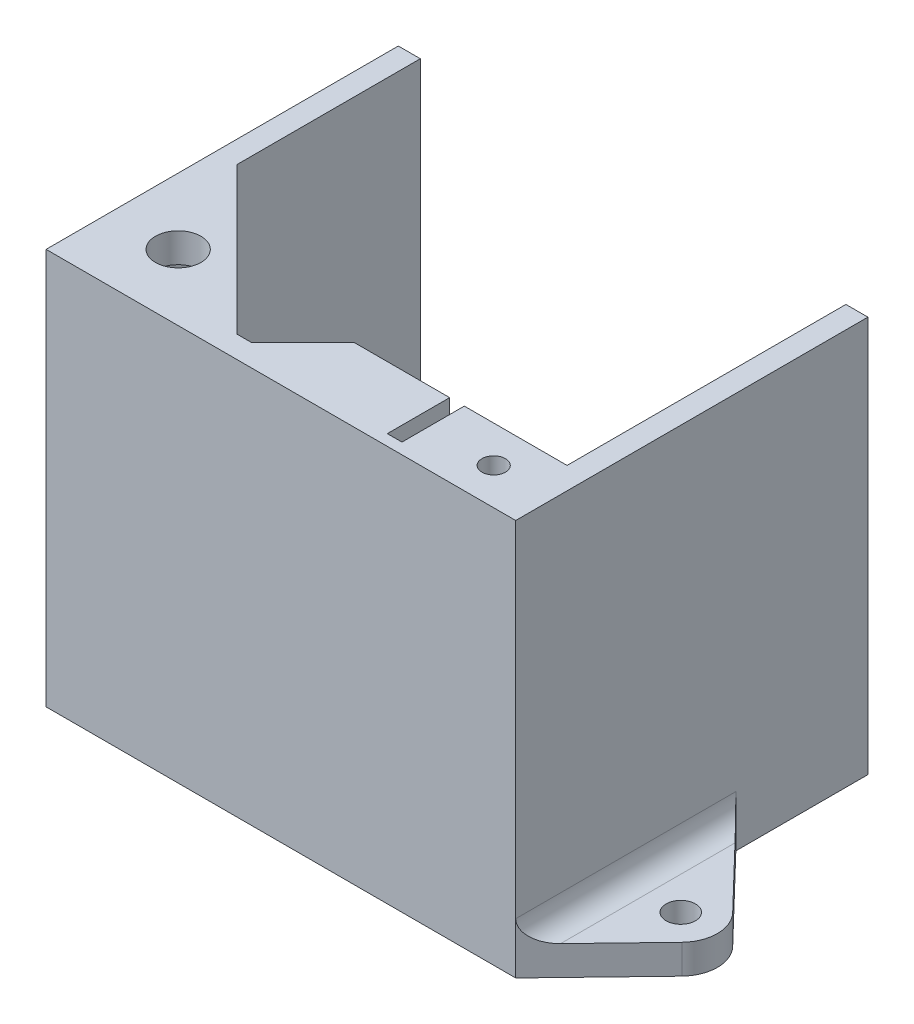
SolidWorks part; units mm, degrees
ref_plane "Płaszczyzna przednia" through (0, 0, 0) normal (0, 0, 1) x (1, 0, 0)
ref_plane "Płaszczyzna górna" through (0, 0, 0) normal (0, 1, 0) x (1, 0, 0)
ref_plane "Płaszczyzna prawa" through (0, 0, 0) normal (1, 0, 0) x (0, 0, -1)
sketch "Sketch1" plane through (0, 0, 0) normal (0, 1, 0) x (1, 0, 0)
  line L1 (-32, 24) -> (32, 24)
  line L2 (-32, 24) -> (-32, -24)
  line L3 (-32, -24) -> (32, -24)
  line L4 (32, 24) -> (32, -24)
  line L5 (-32, 24) -> (32, -24) construction
  line L6 (-32, -24) -> (32, 24) construction
  point P0 (0, 0)
  dimension "D1" = 64
  dimension "D2" = 48
extrude "Boss-Extrude1" add sketch "Sketch1" along normal blind 4
sketch "Sketch2" plane through (0, 0, 0) normal (0, -1, 0) x (1, 0, 0)
  line L9 (-20.6514, -16) -> (-22.3257, -13.1)
  line L10 (-22.3257, -13.1) -> (-25.6743, -13.1)
  line L11 (-25.6743, -13.1) -> (-27.3486, -16)
  line L12 (-27.3486, -16) -> (-25.6743, -18.9)
  line L13 (-25.6743, -18.9) -> (-22.3257, -18.9)
  line L14 (-22.3257, -18.9) -> (-20.6514, -16)
  line L15 (-32, -24) -> (-32, 24) construction
  line L16 (32, -24) -> (-32, -24) construction
  circle A0 centre (-24, -16) radius 2.9 construction
  dimension "D3" = 5.8
  dimension "D1" = 8
  dimension "D2" = 8
extrude "Cut-Extrude1" cut sketch "Sketch2" against normal blind 2.4
sketch "Sketch4" plane through (0, 0, 0) normal (0, -1, 0) x (1, 0, 0)
  line L0 (-32, -24) -> (-32, 24) construction
  line L1 (9.3486, 10) -> (7.6743, 12.9)
  line L2 (7.6743, 12.9) -> (4.3257, 12.9)
  line L3 (4.3257, 12.9) -> (2.6514, 10)
  line L4 (2.6514, 10) -> (4.3257, 7.1)
  line L5 (4.3257, 7.1) -> (7.6743, 7.1)
  line L6 (7.6743, 7.1) -> (9.3486, 10)
  line L8 (32, -24) -> (-32, -24) construction
  circle A0 centre (6, 10) radius 2.9 construction
  dimension "D3" = 5.8
  dimension "D1" = 38
  dimension "D2" = 34
extrude "Cut-Extrude2" cut sketch "Sketch4" against normal blind 2.4
sketch "Sketch6" plane through (0, 4, 0) normal (0, 1, 0) x (1, 0, 0)
  line L0 (-29, 21) -> (-29, 24)
  line L1 (-32, 24) -> (32, 24)
  line L2 (-32, 24) -> (-32, -24)
  line L3 (-32, -24) -> (32, -24)
  line L4 (32, 24) -> (32, -24)
  line L5 (-29, 21) -> (29, 21)
  line L6 (-29, 21) -> (-29, -21)
  line L7 (-29, -21) -> (29, -21)
  line L8 (29, 21) -> (29, -21)
  line L9 (-29, 21) -> (29, -21) construction
  line L10 (-29, -21) -> (29, 21) construction
  line L11 (29, 21) -> (29, 24)
  point P6 (0, 0)
  line M1 (32, -24) -> (32, 24)
  line M2 (32, 24) -> (-32, 24)
  line M3 (-32, 24) -> (-32, -24)
  line M4 (-32, -24) -> (32, -24)
  dimension "D1" = 58
  dimension "D2" = 42
extrude "Boss-Extrude3" add sketch "Sketch6" along normal blind 50 contours L11 L8 L7 L6 L0 M2 M3 M4 M1 region at (-29.8, 4, 0)
sketch "Sketch9" plane through (0, 4, 0) normal (0, 1, 0) x (1, 0, 0)
  line L0 (1, -13) -> (-7, -21)
  line L3 (29, -13) -> (1, -13)
  line L5 (-29, -21) -> (29, -21) construction
  line L6 (-7, -21) -> (29, -21)
  line L7 (1, -13) -> (-7, -21)
  line L9 (29, -21) -> (29, -13)
  line M3 (29, -21) -> (29, 24)
  line M6 (-29, -21) -> (29, -21)
  dimension "D1" = 8
  dimension "D2" = 8
  dimension "D3" = 28
extrude "Boss-Extrude4" add sketch "Sketch9" along normal blind 50 contours L3 L0 M3 M6 region at (12.9167, 4, 17.1667)
sketch "Sketch10" plane through (0, 0, 13) normal (0, 0, -1) x (-1, 0, 0)
  line L0 (-29, 54) -> (-29, 4) construction
  line L1 (-27, 39) -> (-1, 39)
  line L2 (-27, 39) -> (-27, 13)
  line L3 (-27, 13) -> (-1, 13)
  line L4 (-1, 39) -> (-1, 13)
  line L5 (-27, 39) -> (-1, 13) construction
  line L6 (-27, 13) -> (-1, 39) construction
  line L7 (-14, 39) -> (-14, 54) construction
  line L9 (-29, 54) -> (-1, 54) construction
  line L15 (-14.9986, 39) -> (-13.0014, 39)
  line L16 (-14.9986, 39) -> (-14.9986, 54)
  line L17 (-14.9986, 54) -> (-13.0014, 54)
  line L18 (-13.0014, 39) -> (-13.0014, 54)
  line L19 (-14.9986, 39) -> (-13.0014, 54) construction
  line L20 (-14.9986, 54) -> (-13.0014, 39) construction
  point P0 (-14, 26)
  point P9 (-14, 46.5)
  line M4 (-1, 4) -> (-1, 54)
  line M5 (-1, 54) -> (-29, 54)
  dimension "D1" = 26
  dimension "D2" = 26
  dimension "D3" = 15
  dimension "D5" = 28
extrude "Cut-Extrude4" cut sketch "Sketch10" against normal blind 9.5 contours L2 L3 L1 M4 | L1 M5 region at (14, 26, 13) region at (14, 46.5, 13)
sketch "Sketch13" plane through (0, 54, 0) normal (0, 1, 0) x (1, 0, 0)
  line L1 (29, -13) -> (-7.9463, -13)
  line L2 (29, -13) -> (29, -14)
  line L3 (29, -14) -> (-7.9463, -14)
  line L4 (-7.9463, -13) -> (-7.9463, -14)
  dimension "D1" = 1
extrude "Cut-Extrude6" cut sketch "Sketch13" against normal blind 32
sketch "Sketch15" plane through (0, 54, 0) normal (0, 1, 0) x (1, 0, 0)
  line L0 (-29, -1) -> (-9, -21)
  line L5 (-29, 24) -> (-29, -21) construction
  line L6 (-29, -21) -> (-7, -21) construction
  line L7 (-29, 24) -> (-29, -21) construction
  line L8 (-29, -1) -> (-29, -21)
  line L9 (-29, -21) -> (-9, -21)
  line L10 (-32, 24) -> (-32, -24) construction
  line L11 (-32, -24) -> (32, -24) construction
  circle A0 centre (-23, -15) radius 3.1
  dimension "D3" = 9
  dimension "D1" = 20
  dimension "D2" = 20
  dimension "D4" = 9
extrude "Boss-Extrude5" add sketch "Sketch15" against normal blind 4
sketch "Sketch17" plane through (0, 54, 0) normal (0, 1, 0) x (1, 0, 0)
  line L0 (32, -24) -> (32, 24) construction
  line L7 (-32, -24) -> (32, -24) construction
  line L8 (24, -19) -> (24, -24) construction
  line L9 (24, -19) -> (32, -19) construction
  line L11 (24, -15.8246) -> (21.25, -17.4123)
  line L12 (21.25, -17.4123) -> (21.25, -20.5877)
  line L13 (21.25, -20.5877) -> (24, -22.1754)
  line L14 (24, -22.1754) -> (26.75, -20.5877)
  line L15 (26.75, -20.5877) -> (26.75, -17.4123)
  line L16 (26.75, -17.4123) -> (24, -15.8246)
  circle A0 centre (24, -19) radius 2.75 construction
  dimension "D1" = 8
  dimension "D2" = 5
extrude "Cut-Extrude7" cut sketch "Sketch17" against normal blind 7
sketch "Sketch18" plane through (0, 0, 14) normal (0, 0, -1) x (-1, 0, 0)
  line L0 (-14.9986, 54) -> (-29, 54) construction
  line L1 (-26.8, 49.5) -> (-21.2, 49.5)
  line L2 (-26.8, 49.5) -> (-26.8, 47)
  line L3 (-26.8, 47) -> (-21.2, 47)
  line L4 (-21.2, 49.5) -> (-21.2, 47)
  line L5 (-32, 54) -> (-32, 0) construction
  point P6 (-24, 49.5)
  dimension "D1" = 7
  dimension "D2" = 2.5
  dimension "D3" = 5.6
  dimension "D4" = 8
extrude "Cut-Extrude8" cut sketch "Sketch18" against normal blind 5
sketch "Sketch19" plane through (0, 54, 0) normal (0, 1, 0) x (1, 0, 0)
  line L0 (24, -22.1754) -> (24, -15.8246) construction
  line L5 (26.75, -17.4123) -> (24, -15.8246) construction
  line L6 (24, -15.8246) -> (26.75, -19) construction
  line L7 (26.75, -20.5877) -> (26.75, -17.4123) construction
  line L8 (26.75, -19) -> (21.25, -19) construction
  line L10 (20.7023, -15.4012) -> (27.2977, -15.4012)
  line L11 (20.7023, -15.4012) -> (20.7023, -22.5988)
  line L12 (20.7023, -22.5988) -> (27.2977, -22.5988)
  line L13 (27.2977, -15.4012) -> (27.2977, -22.5988)
  line L14 (20.7023, -15.4012) -> (27.2977, -22.5988) construction
  line L15 (20.7023, -22.5988) -> (27.2977, -15.4012) construction
  circle A0 centre (24, -19) radius 1.6
extrude "Boss-Extrude8" add sketch "Sketch19" against normal blind 4.5
fillet "Fillet1" radius 1.5 2 edges at (-29, 50, 11) (-19, 50, 21)
sketch "Sketch20" plane through (0, 0, 0) normal (0, -1, 0) x (1, 0, 0)
  line L0 (32, 24) -> (43.1021, 12.4677)
  line L1 (39.5, 9) -> (32, 9) construction
  line L2 (32, -6) -> (43.1021, 5.5323)
  line L3 (-32, -24) -> (-42.9789, -14.5912)
  line L4 (32, -6) -> (32, 24)
  line L6 (-32, 2) -> (-32, -24)
  line L8 (-39.5, -11) -> (-32, -11) construction
  line L9 (-32, 2) -> (-42.9789, -7.4088)
  line L10 (-20.8246, -16) -> (-22.4123, -13.25) construction
  line L11 (-22.4123, -18.75) -> (-20.8246, -16) construction
  line L12 (-25.5877, -18.75) -> (-22.4123, -18.75) construction
  line L13 (-27.1754, -16) -> (-25.5877, -18.75) construction
  line L14 (-25.5877, -13.25) -> (-27.1754, -16) construction
  line L15 (-22.4123, -13.25) -> (-25.5877, -13.25) construction
  line L16 (9.1754, 10) -> (7.5877, 12.75) construction
  line L17 (7.5877, 7.25) -> (9.1754, 10) construction
  line L18 (4.4123, 7.25) -> (7.5877, 7.25) construction
  line L19 (2.8246, 10) -> (4.4123, 7.25) construction
  line L20 (4.4123, 12.75) -> (2.8246, 10) construction
  line L21 (7.5877, 12.75) -> (4.4123, 12.75) construction
  line L22 (-22.3257, -13.1) -> (-25.6743, -13.1) construction
  line L23 (-20.6514, -16) -> (-22.3257, -13.1) construction
  line L24 (-22.3257, -13.1) -> (-25.6743, -13.1) construction
  line L25 (-20.6514, -16) -> (-22.3257, -13.1) construction
  line L26 (32, -24) -> (32, 24)
  line L27 (32, 24) -> (-32, 24)
  line L28 (-32, 24) -> (-32, -24)
  line L29 (-32, -24) -> (32, -24)
  line L30 (32, -6) -> (32, 24)
  line L32 (-32, 2) -> (-32, -24)
  line L36 (9.3486, 10) -> (7.6743, 12.9)
  line L37 (7.6743, 7.1) -> (9.3486, 10)
  line L38 (4.3257, 7.1) -> (7.6743, 7.1)
  line L39 (2.6514, 10) -> (4.3257, 7.1)
  line L40 (4.3257, 12.9) -> (2.6514, 10)
  line L41 (7.6743, 12.9) -> (4.3257, 12.9)
  line L42 (9.3486, 10) -> (7.6743, 12.9) construction
  line L43 (7.6743, 7.1) -> (9.3486, 10) construction
  line L44 (4.3257, 7.1) -> (7.6743, 7.1) construction
  line L45 (2.6514, 10) -> (4.3257, 7.1) construction
  line L46 (4.3257, 12.9) -> (2.6514, 10) construction
  line L47 (7.6743, 12.9) -> (4.3257, 12.9) construction
  line L48 (-20.6514, -16) -> (-22.3257, -13.1)
  line L49 (-22.3257, -18.9) -> (-20.6514, -16)
  line L50 (-25.6743, -18.9) -> (-22.3257, -18.9)
  line L51 (-27.3486, -16) -> (-25.6743, -18.9)
  line L52 (-25.6743, -13.1) -> (-27.3486, -16)
  line L53 (-22.3257, -13.1) -> (-25.6743, -13.1)
  line L54 (-20.6514, -16) -> (-22.3257, -13.1) construction
  line L55 (-22.3257, -18.9) -> (-20.6514, -16) construction
  line L56 (-25.6743, -18.9) -> (-22.3257, -18.9) construction
  line L57 (-27.3486, -16) -> (-25.6743, -18.9) construction
  line L58 (-25.6743, -13.1) -> (-27.3486, -16) construction
  line L59 (-22.3257, -13.1) -> (-25.6743, -13.1) construction
  circle A0 centre (39.5, 9) radius 2
  circle A1 centre (-39.5, -11) radius 2
  arc A2 (43.1021, 5.5323) -> (43.1021, 12.4677) centre (39.5, 9) ccw
  arc A3 (-42.5162, -7.0122) -> (-42.5162, -14.9878) centre (-39.5, -11) ccw
  dimension "D1" = 0
  dimension "D2" = 0
  dimension "D3" = 0
extrude "Boss-Extrude9" add sketch "Sketch20" against normal blind 4 contours L9 A3 L3 L23 A1 | L2 A2 L0 L4 A0 region at (36.4432, 0, 9) region at (-36.5396, 0, -11)
fillet "Fillet2" radius 3 2 edges at (-32, 4, -11) (32, 4, 9)
sketch "Sketch22" plane through (0, 2.4, 0) normal (0, -1, 0) x (1, 0, 0)
  line L0 (4.3257, 12.9) -> (7.6743, 7.1) construction
  line L1 (7.6743, 7.1) -> (7.6743, 12.9) construction
  line L2 (7.6743, 12.9) -> (4.3257, 7.1) construction
  line L3 (-25.6743, -18.9) -> (-22.3257, -13.1) construction
  line L4 (-22.3257, -13.1) -> (-22.3257, -18.9) construction
  line L5 (-25.6743, -13.1) -> (-22.3257, -18.9) construction
  circle A0 centre (-24, -16) radius 1.65
  circle A1 centre (6, 10) radius 1.65
  dimension "D1" = 3.3
  dimension "D2" = 3.3
extrude "Cut-Extrude9" cut sketch "Sketch22" against normal blind 2
